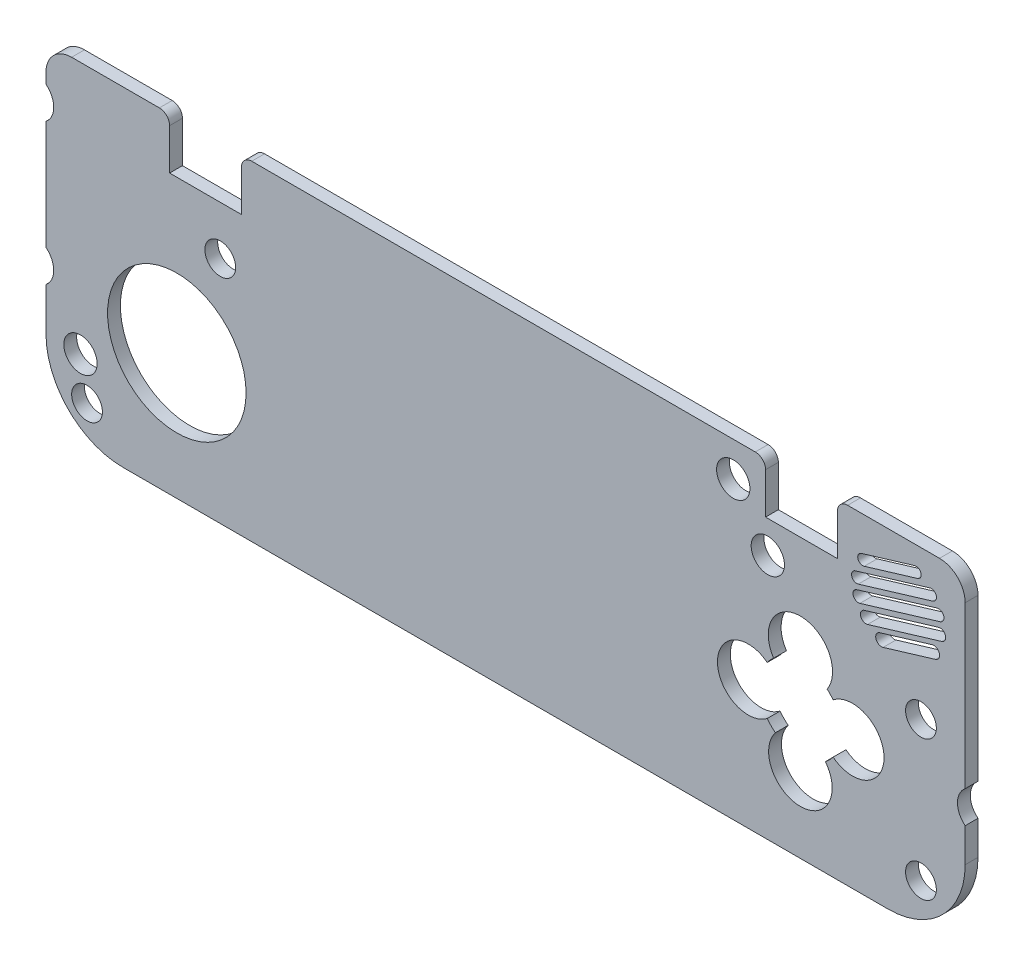
SolidWorks part; units mm, degrees
ref_plane "Plan de face" through (0, 0, 0) normal (0, 0, 1) x (1, 0, 0)
ref_plane "Plan de dessus" through (0, 0, 0) normal (0, 1, 0) x (1, 0, 0)
ref_plane "Plan de droite" through (0, 0, 0) normal (1, 0, 0) x (0, 0, -1)
sketch "Esquisse1" plane through (0, 0, 0) normal (0, 0, 1) x (1, 0, 0)
  line L1 (-89.2039, 33.3448) -> (79.9661, 33.3448)
  line L2 (-94.2039, 28.3448) -> (-94.2039, -15.8852)
  line L3 (-79.2039, -30.8852) -> (69.9661, -30.8852)
  line L4 (84.9661, 28.3448) -> (84.9661, -15.8852)
  arc A0 (-89.2039, 33.3448) -> (-94.2039, 28.3448) centre (-89.2039, 28.3448) ccw
  arc A1 (79.9661, 33.3448) -> (84.9661, 28.3448) centre (79.9661, 28.3448) cw
  arc A2 (69.9661, -30.8852) -> (84.9661, -15.8852) centre (69.9661, -15.8852) ccw
  arc A3 (-94.2039, -15.8852) -> (-79.2039, -30.8852) centre (-79.2039, -15.8852) ccw
  point P6 (-94.2039, 33.3448)
  point P9 (84.9661, 33.3448)
  point P12 (84.9661, -30.8852)
  dimension "D3" = 5
  dimension "D4" = 5
  dimension "D5" = 15
  dimension "D6" = 15
  dimension "D1" = 179.17
  dimension "D2" = 64.23
extrude "Boss.-Extru.1" add sketch "Esquisse1" along normal blind 2.5 contours L1 A1 L4 A2 L3 A3 L2 A0
sketch "12x12 Button" plane through (0, 0, 2.5) normal (0, 0, 1) x (1, 0, 0)
  line L0 (84.9661, 28.3448) -> (84.9661, -15.8852) construction
  line L1 (-79.2039, -30.8852) -> (69.9661, -30.8852) construction
  line L2 (52.8461, 3.7748) -> (52.8461, -15.9152)
  line L3 (42.6861, -5.7552) -> (63.0061, -5.7552)
  circle A0 centre (42.6861, -5.7552) radius 5.9988
  circle A1 centre (52.8461, 3.7748) radius 6.2634
  circle A2 centre (52.8461, -15.9152) radius 6.1927
  circle A3 centre (63.0061, -5.7552) radius 6.14
  arc A5 (46.3825, -1.0306) -> (47.6252, 0.3146) centre (52.8461, -5.7552) cw
  arc A6 (59.2204, -0.9212) -> (58.0635, 0.3093) centre (52.8461, -5.7552) ccw
  arc A7 (46.3874, -10.476) -> (47.9701, -12.0975) centre (52.8461, -5.7552) ccw
  arc A10 (57.722, -12.0975) -> (59.2204, -10.5893) centre (52.8461, -5.7552) ccw
  dimension "D1" = 21.96
  dimension "D2" = 32.12
  dimension "D3" = 42.28
  dimension "D4" = 32.12
  dimension "D5" = 14.97
  dimension "D6" = 34.66
  dimension "D7" = 25.13
  dimension "D8" = 25.13
extrude "Enlèv. mat.-Extru.14" cut sketch "12x12 Button" against normal blind 10 contours A0 | A1 | A5 A0 L3 L2 A1 | A0 A7 A2 L2 L3 | A2 A10 A3 L3 L2 | A3 A6 A1 L2 L3 | A2 | A3 region at (55.6454, -3.3252, 2.5) region at (49.9662, -3.3183, 2.5) region at (49.9669, -1.5874, 2.5) region at (55.6071, -8.4886, 2.5) region at (50.0167, -8.4832, 2.5) region at (55.4812, -10.5053, 2.5) region at (47.9275, -8.306, 2.5) region at (57.6421, -3.1428, 2.5)
sketch "Joystick" plane through (0, 0, 2.5) normal (0, 0, 1) x (1, 0, 0)
  line L0 (-79.2039, -30.8852) -> (69.9661, -30.8852) construction
  line L1 (-94.2039, 28.3448) -> (-94.2039, -15.8852) construction
  circle A0 centre (-68.7039, -6.3252) radius 13.5
  dimension "D1" = 24.56
  dimension "D2" = 25.5
extrude "Enlèv. mat.-Extru.2" cut sketch "Joystick" against normal blind 2.5
sketch "Esquisse2" plane through (0, 0, 2.5) normal (0, 0, 1) x (1, 0, 0)
  line L0 (-89.2039, 33.3448) -> (79.9661, 33.3448) construction
  line L1 (46.0561, 33.3448) -> (60.0561, 33.3448)
  line L2 (46.0561, 33.3448) -> (46.0561, 23.3448)
  line L3 (46.0561, 23.3448) -> (60.0561, 23.3448)
  line L4 (60.0561, 33.3448) -> (60.0561, 23.3448)
  line L5 (84.9661, 28.3448) -> (84.9661, -15.8852) construction
  dimension "D1" = 24.91
  dimension "D2" = 14
extrude "Enlèv. mat.-Extru.3" cut sketch "Esquisse2" against normal blind 10
fillet "Congé1" radius 2 1 edges at (46.0561, 33.3448, 1.25)
fillet "Congé2" radius 2 1 edges at (60.0561, 33.3448, 1.25)
sketch "Esquisse3" plane through (0, 0, 2.5) normal (0, 0, 1) x (1, 0, 0)
  line L0 (-89.2039, 33.3448) -> (44.0561, 33.3448) construction
  line L1 (-70.1039, 33.3448) -> (-56.1039, 33.3448)
  line L2 (-70.1039, 33.3448) -> (-70.1039, 23.3448)
  line L3 (-70.1039, 23.3448) -> (-56.1039, 23.3448)
  line L4 (-56.1039, 33.3448) -> (-56.1039, 23.3448)
  line L5 (-94.2039, 28.3448) -> (-94.2039, -15.8852) construction
  dimension "D1" = 24.1
  dimension "D2" = 10
  dimension "D3" = 14
extrude "Enlèv. mat.-Extru.4" cut sketch "Esquisse3" against normal blind 10 contours L2 L1 L4 L3
fillet "Congé3" radius 2 1 edges at (-70.1039, 33.3448, 1.25)
fillet "Congé4" radius 2 1 edges at (-56.1039, 33.3448, 1.25)
sketch "Esquisse4" plane through (0, 0, 2.5) normal (0, 0, 1) x (1, 0, 0)
  line L0 (84.9661, 28.3448) -> (84.9661, -15.8852) construction
  line L1 (64.1511, 18.9874) -> (79.781, 23.7022) construction
  line L2 (62.0561, 33.3448) -> (79.9661, 33.3448) construction
  line L3 (63.8482, 19.9918) -> (79.478, 24.7066)
  line L4 (64.4541, 17.983) -> (80.084, 22.6978)
  line L5 (63.8337, 22.048) -> (78.3531, 26.4278) construction
  line L6 (63.5398, 23.0223) -> (78.0592, 27.4021)
  line L7 (64.1276, 21.0736) -> (78.647, 25.4535)
  line L8 (65.0061, 25.6097) -> (75.4066, 28.7471) construction
  line L9 (64.7213, 26.554) -> (75.1217, 29.6914)
  line L10 (65.291, 24.6654) -> (75.6914, 27.8027)
  line L11 (65.627, 16.2022) -> (80.0915, 20.5654) construction
  line L12 (65.3147, 17.2374) -> (79.7793, 21.6007)
  line L13 (65.9393, 15.1669) -> (80.4038, 19.5302)
  line L14 (68.6474, 13.8871) -> (78.8552, 16.9663) construction
  line L15 (68.3228, 14.9633) -> (78.5305, 18.0425)
  line L16 (68.9721, 12.8109) -> (79.1798, 15.8901)
  circle A0 centre (71.9661, 21.3448) radius 10
  circle A1 centre (71.9661, 21.3448) radius 8.1628
  arc A2 (63.8482, 19.9918) -> (64.4541, 17.983) centre (64.1511, 18.9874) ccw
  arc A3 (80.084, 22.6978) -> (79.478, 24.7066) centre (79.781, 23.7022) ccw
  arc A4 (63.5398, 23.0223) -> (64.1276, 21.0736) centre (63.8337, 22.048) ccw
  arc A5 (78.647, 25.4535) -> (78.0592, 27.4021) centre (78.3531, 26.4278) ccw
  arc A6 (64.7213, 26.554) -> (65.291, 24.6654) centre (65.0061, 25.6097) ccw
  arc A7 (75.6914, 27.8027) -> (75.1217, 29.6914) centre (75.4066, 28.7471) ccw
  arc A8 (65.3147, 17.2374) -> (65.9393, 15.1669) centre (65.627, 16.2022) ccw
  arc A9 (80.4038, 19.5302) -> (79.7793, 21.6007) centre (80.0915, 20.5654) ccw
  arc A10 (68.3228, 14.9633) -> (68.9721, 12.8109) centre (68.6474, 13.8871) ccw
  arc A11 (79.1798, 15.8901) -> (78.5305, 18.0425) centre (78.8552, 16.9663) ccw
  point P9 (71.9661, 21.3448)
  point P16 (71.0934, 24.2379)
  point P25 (70.2064, 27.1784)
  point P36 (72.8593, 18.3838)
  point P47 (73.7513, 15.4267)
  dimension "D1" = 13
  dimension "D2" = 12
  dimension "D4" = 0
  dimension "D5" = 1.0673
  dimension "D6" = 360
  dimension "D7" = 360
  dimension "D8" = 0.8833
extrude "Enlèv. mat.-Extru.8" cut sketch "Esquisse4" against normal blind 10 contours L4 A1 L3 | L3 A2 A0 L4 A1 | L6 A4 A0 A1 | L9 A6 A0 A1 | L10 A7 A1 L9 A6 | A1 A9 L12 A8 L13 | A1 A8 A0 L13 | A1 A10 A0 L16 | A1 A11 L15 A10 L16 | L16 A11 A0 A1 | A0 A9 A1 L13 | A0 A3 L3 A1 L4 | A0 A5 L6 A1 | L7 A5 A1 L6 A4 | A0 A7 L9 A1 region at (63.7367, 18.8624, 2.5) region at (71.9661, 21.3448, 2.5) region at (80.1954, 23.8272, 2.5) region at (63.4195, 22.0941, 2.5) region at (71.0986, 24.2207, 2.5) region at (78.6726, 26.6952, 2.5) region at (72.8532, 18.4038, 2.5) region at (65.2917, 15.9147, 2.5) region at (80.5298, 20.5113, 2.5) region at (64.7542, 25.9173, 2.5) region at (70.2242, 27.1192, 2.5) region at (75.4463, 29.1426, 2.5) region at (73.7264, 15.5093, 2.5) region at (68.6334, 13.4338, 2.5) region at (79.1175, 16.5964, 2.5)
sketch "Esquisse5" plane through (0, 0, 2.5) normal (0, 0, 1) x (1, 0, 0)
  line L0 (84.9661, 28.3448) -> (84.9661, -15.8852) construction
  line L1 (-79.2039, -30.8852) -> (69.9661, -30.8852) construction
  line L2 (-94.2039, 28.3448) -> (-94.2039, -15.8852) construction
  line L7 (62.0561, 33.3448) -> (79.9661, 33.3448) construction
  line L8 (-54.1039, 33.3448) -> (44.0561, 33.3448) construction
  circle A0 centre (76.3461, -22.8852) radius 3
  circle A1 centre (-86.2039, -23.5352) radius 3
  circle A2 centre (76.3461, 4.3448) radius 3
  circle A3 centre (-60.2339, 13.8348) radius 3
  circle A4 centre (-87.4839, -15.9152) radius 3.25
  circle A5 centre (39.7561, 26.6248) radius 3.25
  circle A6 centre (46.4961, 17.1048) radius 3.25
  dimension "D1" = 8.62
  dimension "D3" = 7.35
  dimension "D5" = 8.62
  dimension "D7" = 19.51
  dimension "D9" = 6.72
  dimension "D11" = 6.72
  dimension "D13" = 38.47
  dimension "D2" = 8
  dimension "D4" = 8
  dimension "D6" = 29
  dimension "D8" = 33.97
  dimension "D10" = 14.97
  dimension "D12" = 45.21
  dimension "D14" = 16.24
extrude "Enlèv. mat.-Extru.9" cut sketch "Esquisse5" against normal blind 10
sketch "Esquisse6" plane through (0, 0, 2.5) normal (0, 0, 1) x (1, 0, 0)
  line L0 (-76.1808, -30.8852) -> (-76.1808, -4.3852)
  line L1 (-79.2039, -30.8852) -> (69.9661, -30.8852) construction
  line L2 (-76.1808, -4.3852) -> (-94.2039, -4.3852)
  line L3 (-94.2039, 28.3448) -> (-94.2039, -15.8852) construction
  line L4 (-94.2039, -4.3852) -> (-99.2039, -4.3852)
  line L5 (-80.6539, 33.3448) -> (-80.6539, 23.1548)
  line L6 (-89.2039, 33.3448) -> (-72.1039, 33.3448) construction
  line L7 (-80.6539, 23.1548) -> (-94.2039, 23.1548)
  line L8 (-94.2039, 23.1548) -> (-99.2039, 23.1548)
  line L9 (68.4263, -30.8852) -> (68.4263, -6.1652)
  line L10 (68.4263, -6.1652) -> (84.9661, -6.1652)
  line L11 (84.9661, 28.3448) -> (84.9661, -15.8852) construction
  line L12 (84.9661, -6.1652) -> (89.9661, -6.1652)
  circle A0 centre (-96.7039, -4.3852) radius 4
  circle A1 centre (-96.7039, 23.1548) radius 4
  circle A2 centre (87.4661, -6.1652) radius 4
extrude "Enlèv. mat.-Extru.15" cut sketch "Esquisse6" against normal blind 10
